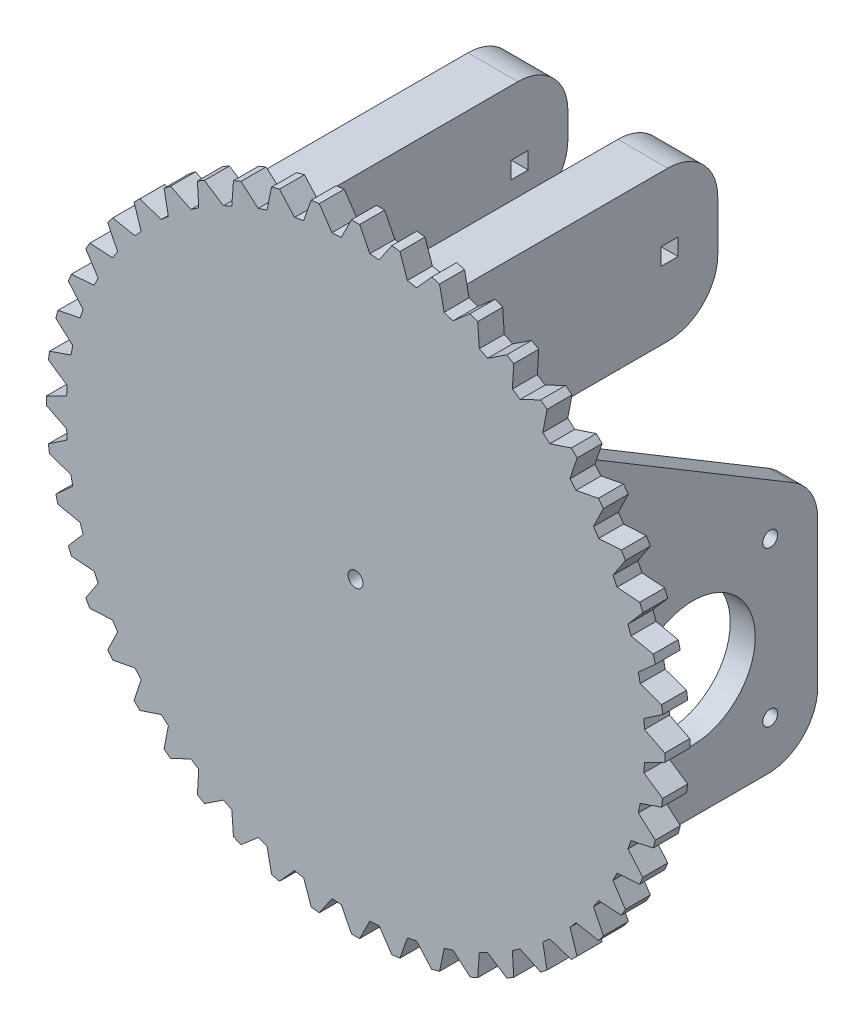
SolidWorks part; units mm, degrees
ref_plane "Front Plane" through (0, 0, 0) normal (0, 0, 1) x (1, 0, 0)
ref_plane "Top Plane" through (0, 0, 0) normal (0, 1, 0) x (1, 0, 0)
ref_plane "Right Plane" through (0, 0, 0) normal (1, 0, 0) x (0, 0, -1)
sketch "Sketch1" plane through (0, 0, 0) normal (0, 0, 1) x (1, 0, 0)
  circle A0 centre (0, 0) radius 60
  circle A1 centre (0, 0) radius 1.5
  dimension "D1" = 120
  dimension "D2" = 3
extrude "Boss-Extrude1" add sketch "Sketch1" along normal blind 5
sketch "Sketch2" plane through (0, 0, 0) normal (0, 0, -1) x (-1, 0, 0)
  line L0 (37.5, 37.5) -> (-37.5, -37.5) construction
  line L1 (-37.5, 37.5) -> (37.5, -37.5) construction
  line L3 (-37.5, 37.5) -> (-32.5, 37.5)
  line L4 (-37.5, 37.5) -> (-37.5, -37.5)
  line L5 (-37.5, -37.5) -> (-32.5, -37.5)
  line L6 (-32.5, 37.5) -> (-32.5, -37.5)
  line L7 (37.5, 37.5) -> (32.5, 37.5)
  line L8 (37.5, 37.5) -> (37.5, -37.5)
  line L9 (37.5, -37.5) -> (32.5, -37.5)
  line L10 (32.5, 37.5) -> (32.5, -37.5)
  point P7 (0, 0)
  dimension "D1" = 75
  dimension "D2" = 5
extrude "Boss-Extrude2" add sketch "Sketch2" along normal blind 50
sketch "Sketch3" plane through (32.5, 0, 0) normal (-1, 0, 0) x (0, 0, 1)
  line L0 (-50, -37.5) -> (0, 12.5) construction
  line L1 (-50, -37.5) -> (-50, 37.5) construction
  line L2 (-50, -37.5) -> (0, -37.5) construction
  line L3 (0, -37.5) -> (0, 37.5) construction
  line L4 (0, -37.5) -> (-50, 12.5) construction
  circle A0 centre (-40.5, 3) radius 1.5
  circle A1 centre (-9.5, 3) radius 1.5
  circle A2 centre (-9.5, -28) radius 1.5
  circle A3 centre (-40.5, -28) radius 1.5
  circle A4 centre (-25, -12.5) radius 12.5
  dimension "D2" = 3
  dimension "D4" = 25
  dimension "D1" = 45
  dimension "D3" = 31
extrude "Cut-Extrude1" cut sketch "Sketch3" against normal through all
sketch "Sketch6" plane through (-37.5, 0, 0) normal (-1, 0, 0) x (0, 0, 1)
  line L0 (-50, -37.5) -> (0, 12.5) construction
  line L1 (0, -37.5) -> (-50, 12.5) construction
  circle A0 centre (-40.5, 3) radius 1.5
  circle A1 centre (-9.5, 3) radius 1.5
  circle A2 centre (-9.5, -28) radius 1.5
  circle A3 centre (-40.5, -28) radius 1.5
  circle A4 centre (-25, -12.5) radius 12.5
  dimension "D1" = 3
  dimension "D3" = 25
  dimension "D2" = 31
extrude "Cut-Extrude5" cut sketch "Sketch6" against normal up to surface (5 mm away) up to face at (-32.5, 0, -25)
sketch "Sketch7" plane through (-37.5, 0, 0) normal (-1, 0, 0) x (0, 0, 1)
  line L0 (-25, -12.5) -> (-60.3553, 22.8553) construction
  line L1 (0, 60) -> (0, -60) construction
  line L2 (-50, 37.5) -> (-70, 37.5)
  line L3 (-70, 12.5) -> (-50, 12.5)
  line L4 (-50, -37.5) -> (-50, 37.5) construction
  line L5 (-70, 37.5) -> (-70, 12.5)
  line L6 (-50, 12.5) -> (-50, 37.5)
  line L7 (-58.6553, 21.1553) -> (-62.0553, 21.1553)
  line L8 (-58.6553, 21.1553) -> (-58.6553, 24.5553)
  line L9 (-58.6553, 24.5553) -> (-62.0553, 24.5553)
  line L10 (-62.0553, 21.1553) -> (-62.0553, 24.5553)
  line L11 (-58.6553, 21.1553) -> (-62.0553, 24.5553) construction
  line L12 (-58.6553, 24.5553) -> (-62.0553, 21.1553) construction
  circle A2 centre (-25, -12.5) radius 12.5 construction
  point P16 (-60.3553, 22.8553)
  dimension "D3" = 3.4
  dimension "D5" = 20
  dimension "D1" = 50
  dimension "D2" = 45
  dimension "D4" = 25
extrude "Boss-Extrude4" add sketch "Sketch7" against normal blind 5
sketch "Sketch8" plane through (-37.5, 0, 0) normal (-1, 0, 0) x (0, 0, 1)
  line L0 (-25, -12.5) -> (-25, 22.8553) construction
  line L1 (-25, 22.8553) -> (-60.3553, 22.8553) construction
  line L2 (-62.0553, 21.1553) -> (-58.6553, 24.5553) construction
sketch "Sketch10" plane through (0, 0, 0) normal (0, 0, -1) x (-1, 0, 0)
  line L1 (2.5, 37.5) -> (12.5, 37.5)
  line L2 (2.5, 37.5) -> (2.5, 7.5)
  line L3 (2.5, 7.5) -> (12.5, 7.5)
  line L4 (12.5, 37.5) -> (12.5, 7.5)
  line L5 (2.5, 37.5) -> (12.5, 7.5) construction
  line L6 (2.5, 7.5) -> (12.5, 37.5) construction
  line L9 (37.5, 37.5) -> (42.5, 37.5)
  line L10 (37.5, 37.5) -> (37.5, 12.5)
  line L11 (37.5, 12.5) -> (42.5, 12.5)
  line L12 (42.5, 37.5) -> (42.5, 12.5)
  point P0 (7.5, 22.5)
  dimension "D1" = 35
  dimension "D2" = 10
  dimension "D3" = 30
  dimension "D4" = 5
  dimension "D5" = 25
extrude "Boss-Extrude5" add sketch "Sketch10" along normal blind 70
sketch "Sketch13" plane through (-32.5, 0, 0) normal (-1, 0, 0) x (0, 0, 1)
  line L1 (-62.0553, 21.1553) -> (-58.6553, 21.1553)
  line L2 (-62.0553, 21.1553) -> (-62.0553, 24.5553)
  line L3 (-62.0553, 24.5553) -> (-58.6553, 24.5553)
  line L4 (-58.6553, 21.1553) -> (-58.6553, 24.5553)
extrude "Cut-Extrude7" cut sketch "Sketch13" against normal through all and the other way through all
fillet "Fillet1" radius 10 4 edges at (-7.5, 37.5, -70) (-7.5, 7.5, -70) (-37.5, 12.5, -70) (-37.5, 37.5, -70)
sketch "Sketch14" plane through (0, 0, -70) normal (0, 0, -1) x (-1, 0, 0)
  line L0 (12.5, 17.5) -> (2.5, 27.5) construction
  line L1 (7.5, 22.5) -> (37.5, 22.5) construction
  line L2 (32.5, 22.5) -> (42.5, 22.5) construction
  circle A0 centre (7.5, 22.5) radius 1.5
  circle A1 centre (37.5, 22.5) radius 1.5
  dimension "D1" = 3
extrude "Cut-Extrude8" cut sketch "Sketch14" against normal up to surface (11.3447 mm away) up to face at (-37.5, 22.8553, -58.6553)
chamfer "Chamfer1" distance 50 distance2 30 1 edges at (35, 37.5, -50) first distance on face at (35, 37.5, -25)
fillet "Fillet2" radius 10 4 edges at (35, 7.5, -50) (-35, -37.5, -50) (35, -37.5, -50) (-35, 12.5, -50)
sketch "Sketch16" plane through (0, 0, 5) normal (0, 0, 1) x (1, 0, 0)
  line L0 (0, 0) -> (0, 62) construction
  line L1 (0, 0) -> (-3.7934, 57.8758) construction
  line L2 (-3.7934, 57.8758) -> (-2.6384, 57.9515)
  line L3 (-2.6384, 57.9515) -> (-0.5787, 62)
  line L4 (-0.5787, 62) -> (0.5787, 62)
  line L5 (-17.2221, 59.5601) -> (14.0077, 60.3969) construction
  line L6 (-1.6608, 61.9778) -> (-1.5536, 57.9792) construction
  line L7 (2.6384, 57.9515) -> (0.5787, 62)
  line L8 (3.7934, 57.8758) -> (2.6384, 57.9515)
  line L9 (3.7934, 57.8758) -> (4.9483, 57.8001)
  line L10 (4.9483, 57.8001) -> (7.5189, 61.5451)
  line L11 (7.5189, 61.5451) -> (8.6664, 61.394)
  line L12 (10.18, 57.1114) -> (8.6664, 61.394)
  line L13 (11.3152, 56.8855) -> (10.18, 57.1114)
  line L14 (11.3152, 56.8855) -> (12.4504, 56.6597)
  line L15 (12.4504, 56.6597) -> (15.4878, 60.0372)
  line L16 (15.4878, 60.0372) -> (16.6058, 59.7376)
  line L17 (17.5475, 55.294) -> (16.6058, 59.7376)
  line L18 (18.6435, 54.9219) -> (17.5475, 55.294)
  line L19 (18.6435, 54.9219) -> (19.7395, 54.5499)
  line L20 (19.7395, 54.5499) -> (23.1917, 57.502)
  line L21 (23.1917, 57.502) -> (24.261, 57.0591)
  line L22 (24.6147, 52.5305) -> (24.261, 57.0591)
  line L23 (25.6527, 52.0186) -> (24.6147, 52.5305)
  line L24 (25.6527, 52.0186) -> (26.6908, 51.5067)
  line L25 (26.6908, 51.5067) -> (30.4988, 53.9829)
  line L26 (30.4988, 53.9829) -> (31.5012, 53.4042)
  line L27 (31.2607, 48.8683) -> (31.5012, 53.4042)
  line L28 (32.2231, 48.2252) -> (31.2607, 48.8683)
  line L29 (32.2231, 48.2252) -> (33.1855, 47.5822)
  line L30 (33.1855, 47.5822) -> (37.2841, 49.5402)
  line L31 (37.2841, 49.5402) -> (38.2023, 48.8356)
  line L32 (37.3718, 44.3699) -> (38.2023, 48.8356)
  line L33 (38.2421, 43.6067) -> (37.3718, 44.3699)
  line L34 (38.2421, 43.6067) -> (39.1123, 42.8436)
  line L35 (39.1123, 42.8436) -> (43.4314, 44.2498)
  line L36 (43.4314, 44.2498) -> (44.2498, 43.4314)
  line L37 (42.8436, 39.1123) -> (44.2498, 43.4314)
  line L38 (43.6067, 38.2421) -> (42.8436, 39.1123)
  line L39 (43.6067, 38.2421) -> (44.3699, 37.3718)
  line L40 (44.3699, 37.3718) -> (48.8356, 38.2023)
  line L41 (48.8356, 38.2023) -> (49.5402, 37.2841)
  line L42 (47.5822, 33.1855) -> (49.5402, 37.2841)
  line L43 (48.2252, 32.2231) -> (47.5822, 33.1855)
  line L44 (48.2252, 32.2231) -> (48.8683, 31.2607)
  line L45 (48.8683, 31.2607) -> (53.4042, 31.5012)
  line L46 (53.4042, 31.5012) -> (53.9829, 30.4988)
  line L47 (51.5067, 26.6908) -> (53.9829, 30.4988)
  line L48 (52.0186, 25.6527) -> (51.5067, 26.6908)
  line L49 (52.0186, 25.6527) -> (52.5305, 24.6147)
  line L50 (52.5305, 24.6147) -> (57.0591, 24.261)
  line L51 (57.0591, 24.261) -> (57.502, 23.1917)
  line L52 (54.5499, 19.7395) -> (57.502, 23.1917)
  line L53 (54.9219, 18.6435) -> (54.5499, 19.7395)
  line L54 (54.9219, 18.6435) -> (55.294, 17.5475)
  line L55 (55.294, 17.5475) -> (59.7376, 16.6058)
  line L56 (59.7376, 16.6058) -> (60.0372, 15.4878)
  line L57 (56.6597, 12.4504) -> (60.0372, 15.4878)
  line L58 (56.8855, 11.3152) -> (56.6597, 12.4504)
  line L59 (56.8855, 11.3152) -> (57.1114, 10.18)
  line L60 (57.1114, 10.18) -> (61.394, 8.6664)
  line L61 (61.394, 8.6664) -> (61.5451, 7.5189)
  line L62 (57.8001, 4.9483) -> (61.5451, 7.5189)
  line L63 (57.8758, 3.7934) -> (57.8001, 4.9483)
  line L64 (57.8758, 3.7934) -> (57.9515, 2.6384)
  line L65 (57.9515, 2.6384) -> (62, 0.5787)
  line L66 (62, 0.5787) -> (62, -0.5787)
  line L67 (57.9515, -2.6384) -> (62, -0.5787)
  line L68 (57.8758, -3.7934) -> (57.9515, -2.6384)
  line L69 (57.8758, -3.7934) -> (57.8001, -4.9483)
  line L70 (57.8001, -4.9483) -> (61.5451, -7.5189)
  line L71 (61.5451, -7.5189) -> (61.394, -8.6664)
  line L72 (57.1114, -10.18) -> (61.394, -8.6664)
  line L73 (56.8855, -11.3152) -> (57.1114, -10.18)
  line L74 (56.8855, -11.3152) -> (56.6597, -12.4504)
  line L75 (56.6597, -12.4504) -> (60.0372, -15.4878)
  line L76 (60.0372, -15.4878) -> (59.7376, -16.6058)
  line L77 (55.294, -17.5475) -> (59.7376, -16.6058)
  line L78 (54.9219, -18.6435) -> (55.294, -17.5475)
  line L79 (54.9219, -18.6435) -> (54.5499, -19.7395)
  line L80 (54.5499, -19.7395) -> (57.502, -23.1917)
  line L81 (57.502, -23.1917) -> (57.0591, -24.261)
  line L82 (52.5305, -24.6147) -> (57.0591, -24.261)
  line L83 (52.0186, -25.6527) -> (52.5305, -24.6147)
  line L84 (52.0186, -25.6527) -> (51.5067, -26.6908)
  line L85 (51.5067, -26.6908) -> (53.9829, -30.4988)
  line L86 (53.9829, -30.4988) -> (53.4042, -31.5012)
  line L87 (48.8683, -31.2607) -> (53.4042, -31.5012)
  line L88 (48.2252, -32.2231) -> (48.8683, -31.2607)
  line L89 (48.2252, -32.2231) -> (47.5822, -33.1855)
  line L90 (47.5822, -33.1855) -> (49.5402, -37.2841)
  line L91 (49.5402, -37.2841) -> (48.8356, -38.2023)
  line L92 (44.3699, -37.3718) -> (48.8356, -38.2023)
  line L93 (43.6067, -38.2421) -> (44.3699, -37.3718)
  line L94 (43.6067, -38.2421) -> (42.8436, -39.1123)
  line L95 (42.8436, -39.1123) -> (44.2498, -43.4314)
  line L96 (44.2498, -43.4314) -> (43.4314, -44.2498)
  line L97 (39.1123, -42.8436) -> (43.4314, -44.2498)
  line L98 (38.2421, -43.6067) -> (39.1123, -42.8436)
  line L99 (38.2421, -43.6067) -> (37.3718, -44.3699)
  line L100 (37.3718, -44.3699) -> (38.2023, -48.8356)
  line L101 (38.2023, -48.8356) -> (37.2841, -49.5402)
  line L102 (33.1855, -47.5822) -> (37.2841, -49.5402)
  line L103 (32.2231, -48.2252) -> (33.1855, -47.5822)
  line L104 (32.2231, -48.2252) -> (31.2607, -48.8683)
  line L105 (31.2607, -48.8683) -> (31.5012, -53.4042)
  line L106 (31.5012, -53.4042) -> (30.4988, -53.9829)
  line L107 (26.6908, -51.5067) -> (30.4988, -53.9829)
  line L108 (25.6527, -52.0186) -> (26.6908, -51.5067)
  line L109 (25.6527, -52.0186) -> (24.6147, -52.5305)
  line L110 (24.6147, -52.5305) -> (24.261, -57.0591)
  line L111 (24.261, -57.0591) -> (23.1917, -57.502)
  line L112 (19.7395, -54.5499) -> (23.1917, -57.502)
  line L113 (18.6435, -54.9219) -> (19.7395, -54.5499)
  line L114 (18.6435, -54.9219) -> (17.5475, -55.294)
  line L115 (17.5475, -55.294) -> (16.6058, -59.7376)
  line L116 (16.6058, -59.7376) -> (15.4878, -60.0372)
  line L117 (12.4504, -56.6597) -> (15.4878, -60.0372)
  line L118 (11.3152, -56.8855) -> (12.4504, -56.6597)
  line L119 (11.3152, -56.8855) -> (10.18, -57.1114)
  line L120 (10.18, -57.1114) -> (8.6664, -61.394)
  line L121 (8.6664, -61.394) -> (7.5189, -61.5451)
  line L122 (4.9483, -57.8001) -> (7.5189, -61.5451)
  line L123 (3.7934, -57.8758) -> (4.9483, -57.8001)
  line L124 (3.7934, -57.8758) -> (2.6384, -57.9515)
  line L125 (2.6384, -57.9515) -> (0.5787, -62)
  line L126 (0.5787, -62) -> (-0.5787, -62)
  line L127 (-2.6384, -57.9515) -> (-0.5787, -62)
  line L128 (-3.7934, -57.8758) -> (-2.6384, -57.9515)
  line L129 (-3.7934, -57.8758) -> (-4.9483, -57.8001)
  line L130 (-4.9483, -57.8001) -> (-7.5189, -61.5451)
  line L131 (-7.5189, -61.5451) -> (-8.6664, -61.394)
  line L132 (-10.18, -57.1114) -> (-8.6664, -61.394)
  line L133 (-11.3152, -56.8855) -> (-10.18, -57.1114)
  line L134 (-11.3152, -56.8855) -> (-12.4504, -56.6597)
  line L135 (-12.4504, -56.6597) -> (-15.4878, -60.0372)
  line L136 (-15.4878, -60.0372) -> (-16.6058, -59.7376)
  line L137 (-17.5475, -55.294) -> (-16.6058, -59.7376)
  line L138 (-18.6435, -54.9219) -> (-17.5475, -55.294)
  line L139 (-18.6435, -54.9219) -> (-19.7395, -54.5499)
  line L140 (-19.7395, -54.5499) -> (-23.1917, -57.502)
  line L141 (-23.1917, -57.502) -> (-24.261, -57.0591)
  line L142 (-24.6147, -52.5305) -> (-24.261, -57.0591)
  line L143 (-25.6527, -52.0186) -> (-24.6147, -52.5305)
  line L144 (-25.6527, -52.0186) -> (-26.6908, -51.5067)
  line L145 (-26.6908, -51.5067) -> (-30.4988, -53.9829)
  line L146 (-30.4988, -53.9829) -> (-31.5012, -53.4042)
  line L147 (-31.2607, -48.8683) -> (-31.5012, -53.4042)
  line L148 (-32.2231, -48.2252) -> (-31.2607, -48.8683)
  line L149 (-32.2231, -48.2252) -> (-33.1855, -47.5822)
  line L150 (-33.1855, -47.5822) -> (-37.2841, -49.5402)
  line L151 (-37.2841, -49.5402) -> (-38.2023, -48.8356)
  line L152 (-37.3718, -44.3699) -> (-38.2023, -48.8356)
  line L153 (-38.2421, -43.6067) -> (-37.3718, -44.3699)
  line L154 (-38.2421, -43.6067) -> (-39.1123, -42.8436)
  line L155 (-39.1123, -42.8436) -> (-43.4314, -44.2498)
  line L156 (-43.4314, -44.2498) -> (-44.2498, -43.4314)
  line L157 (-42.8436, -39.1123) -> (-44.2498, -43.4314)
  line L158 (-43.6067, -38.2421) -> (-42.8436, -39.1123)
  line L159 (-43.6067, -38.2421) -> (-44.3699, -37.3718)
  line L160 (-44.3699, -37.3718) -> (-48.8356, -38.2023)
  line L161 (-48.8356, -38.2023) -> (-49.5402, -37.2841)
  line L162 (-47.5822, -33.1855) -> (-49.5402, -37.2841)
  line L163 (-48.2252, -32.2231) -> (-47.5822, -33.1855)
  line L164 (-48.2252, -32.2231) -> (-48.8683, -31.2607)
  line L165 (-48.8683, -31.2607) -> (-53.4042, -31.5012)
  line L166 (-53.4042, -31.5012) -> (-53.9829, -30.4988)
  line L167 (-51.5067, -26.6908) -> (-53.9829, -30.4988)
  line L168 (-52.0186, -25.6527) -> (-51.5067, -26.6908)
  line L169 (-52.0186, -25.6527) -> (-52.5305, -24.6147)
  line L170 (-52.5305, -24.6147) -> (-57.0591, -24.261)
  line L171 (-57.0591, -24.261) -> (-57.502, -23.1917)
  line L172 (-54.5499, -19.7395) -> (-57.502, -23.1917)
  line L173 (-54.9219, -18.6435) -> (-54.5499, -19.7395)
  line L174 (-54.9219, -18.6435) -> (-55.294, -17.5475)
  line L175 (-55.294, -17.5475) -> (-59.7376, -16.6058)
  line L176 (-59.7376, -16.6058) -> (-60.0372, -15.4878)
  line L177 (-56.6597, -12.4504) -> (-60.0372, -15.4878)
  line L178 (-56.8855, -11.3152) -> (-56.6597, -12.4504)
  line L179 (-56.8855, -11.3152) -> (-57.1114, -10.18)
  line L180 (-57.1114, -10.18) -> (-61.394, -8.6664)
  line L181 (-61.394, -8.6664) -> (-61.5451, -7.5189)
  line L182 (-57.8001, -4.9483) -> (-61.5451, -7.5189)
  line L183 (-57.8758, -3.7934) -> (-57.8001, -4.9483)
  line L184 (-57.8758, -3.7934) -> (-57.9515, -2.6384)
  line L185 (-57.9515, -2.6384) -> (-62, -0.5787)
  line L186 (-62, -0.5787) -> (-62, 0.5787)
  line L187 (-57.9515, 2.6384) -> (-62, 0.5787)
  line L188 (-57.8758, 3.7934) -> (-57.9515, 2.6384)
  line L189 (-57.8758, 3.7934) -> (-57.8001, 4.9483)
  line L190 (-57.8001, 4.9483) -> (-61.5451, 7.5189)
  line L191 (-61.5451, 7.5189) -> (-61.394, 8.6664)
  line L192 (-57.1114, 10.18) -> (-61.394, 8.6664)
  line L193 (-56.8855, 11.3152) -> (-57.1114, 10.18)
  line L194 (-56.8855, 11.3152) -> (-56.6597, 12.4504)
  line L195 (-56.6597, 12.4504) -> (-60.0372, 15.4878)
  line L196 (-60.0372, 15.4878) -> (-59.7376, 16.6058)
  line L197 (-55.294, 17.5475) -> (-59.7376, 16.6058)
  line L198 (-54.9219, 18.6435) -> (-55.294, 17.5475)
  line L199 (-54.9219, 18.6435) -> (-54.5499, 19.7395)
  line L200 (-54.5499, 19.7395) -> (-57.502, 23.1917)
  line L201 (-57.502, 23.1917) -> (-57.0591, 24.261)
  line L202 (-52.5305, 24.6147) -> (-57.0591, 24.261)
  line L203 (-52.0186, 25.6527) -> (-52.5305, 24.6147)
  line L204 (-52.0186, 25.6527) -> (-51.5067, 26.6908)
  line L205 (-51.5067, 26.6908) -> (-53.9829, 30.4988)
  line L206 (-53.9829, 30.4988) -> (-53.4042, 31.5012)
  line L207 (-48.8683, 31.2607) -> (-53.4042, 31.5012)
  line L208 (-48.2252, 32.2231) -> (-48.8683, 31.2607)
  line L209 (-48.2252, 32.2231) -> (-47.5822, 33.1855)
  line L210 (-47.5822, 33.1855) -> (-49.5402, 37.2841)
  line L211 (-49.5402, 37.2841) -> (-48.8356, 38.2023)
  line L212 (-44.3699, 37.3718) -> (-48.8356, 38.2023)
  line L213 (-43.6067, 38.2421) -> (-44.3699, 37.3718)
  line L214 (-43.6067, 38.2421) -> (-42.8436, 39.1123)
  line L215 (-42.8436, 39.1123) -> (-44.2498, 43.4314)
  line L216 (-44.2498, 43.4314) -> (-43.4314, 44.2498)
  line L217 (-39.1123, 42.8436) -> (-43.4314, 44.2498)
  line L218 (-38.2421, 43.6067) -> (-39.1123, 42.8436)
  line L219 (-38.2421, 43.6067) -> (-37.3718, 44.3699)
  line L220 (-37.3718, 44.3699) -> (-38.2023, 48.8356)
  line L221 (-38.2023, 48.8356) -> (-37.2841, 49.5402)
  line L222 (-33.1855, 47.5822) -> (-37.2841, 49.5402)
  line L223 (-32.2231, 48.2252) -> (-33.1855, 47.5822)
  line L224 (-32.2231, 48.2252) -> (-31.2607, 48.8683)
  line L225 (-31.2607, 48.8683) -> (-31.5012, 53.4042)
  line L226 (-31.5012, 53.4042) -> (-30.4988, 53.9829)
  line L227 (-26.6908, 51.5067) -> (-30.4988, 53.9829)
  line L228 (-25.6527, 52.0186) -> (-26.6908, 51.5067)
  line L229 (-25.6527, 52.0186) -> (-24.6147, 52.5305)
  line L230 (-24.6147, 52.5305) -> (-24.261, 57.0591)
  line L231 (-24.261, 57.0591) -> (-23.1917, 57.502)
  line L232 (-19.7395, 54.5499) -> (-23.1917, 57.502)
  line L233 (-18.6435, 54.9219) -> (-19.7395, 54.5499)
  line L234 (-18.6435, 54.9219) -> (-17.5475, 55.294)
  line L235 (-17.5475, 55.294) -> (-16.6058, 59.7376)
  line L236 (-16.6058, 59.7376) -> (-15.4878, 60.0372)
  line L237 (-12.4504, 56.6597) -> (-15.4878, 60.0372)
  line L238 (-11.3152, 56.8855) -> (-12.4504, 56.6597)
  line L239 (-11.3152, 56.8855) -> (-10.18, 57.1114)
  line L240 (-10.18, 57.1114) -> (-8.6664, 61.394)
  line L241 (-8.6664, 61.394) -> (-7.5189, 61.5451)
  line L242 (-4.9483, 57.8001) -> (-7.5189, 61.5451)
  line L243 (-3.7934, 57.8758) -> (-4.9483, 57.8001)
  circle A3 centre (0, 0) radius 58
  circle A5 centre (0, 0) radius 62
  circle A6 centre (0, 0) radius 60 construction
  point P8 (-1.6072, 59.9785)
  point P302 (0, 0)
  circle M5 centre (0, 0) radius 1.5
  dimension "D1" = 3.75
  dimension "D2" = 2
  dimension "D3" = 2
  dimension "D4" = 28.5
  dimension "D5" = 48
extrude "Boss-Extrude6" add sketch "Sketch16" against normal up to surface (5 mm away) contours M5 | A5 region at (0, 0, 5) up to face at (-7.5, 22.5, 0)
sketch "Sketch18" plane through (0, 0, 0) normal (0, 0, 1) x (1, 0, 0)
  line L0 (0, 0) -> (0, 62) construction
  line L1 (0, 0) -> (-3.7934, 57.8758) construction
  line L2 (-3.7934, 57.8758) -> (-2.9199, 57.9331)
  line L3 (-2.9199, 57.9331) -> (-0.8754, 62)
  line L4 (-0.8754, 62) -> (0.8754, 62)
  line L5 (-17.5086, 59.4765) -> (13.7168, 60.4636) construction
  line L6 (-1.9591, 61.969) -> (-1.8327, 57.971) construction
  line L7 (2.9199, 57.9331) -> (0.8754, 62)
  line L8 (3.7934, 57.8758) -> (2.9199, 57.9331)
  line L9 (3.7934, 57.8758) -> (4.6669, 57.8186)
  line L10 (4.6669, 57.8186) -> (7.2247, 61.5838)
  line L11 (7.2247, 61.5838) -> (8.9605, 61.3553)
  line L12 (10.4567, 57.0563) -> (8.9605, 61.3553)
  line L13 (11.3152, 56.8855) -> (10.4567, 57.0563)
  line L14 (11.3152, 56.8855) -> (12.1738, 56.7148)
  line L15 (12.1738, 56.7148) -> (15.2012, 60.114)
  line L16 (15.2012, 60.114) -> (16.8923, 59.6608)
  line L17 (17.8146, 55.2033) -> (16.8923, 59.6608)
  line L18 (18.6435, 54.9219) -> (17.8146, 55.2033)
  line L19 (18.6435, 54.9219) -> (19.4724, 54.6406)
  line L20 (19.4724, 54.6406) -> (22.9176, 57.6155)
  line L21 (22.9176, 57.6155) -> (24.5351, 56.9455)
  line L22 (24.8676, 52.4058) -> (24.5351, 56.9455)
  line L23 (25.6527, 52.0186) -> (24.8676, 52.4058)
  line L24 (25.6527, 52.0186) -> (26.4378, 51.6314)
  line L25 (26.4378, 51.6314) -> (30.2419, 54.1313)
  line L26 (30.2419, 54.1313) -> (31.7581, 53.2559)
  line L27 (31.4952, 48.7116) -> (31.7581, 53.2559)
  line L28 (32.2231, 48.2252) -> (31.4952, 48.7116)
  line L29 (32.2231, 48.2252) -> (32.9509, 47.7389)
  line L30 (32.9509, 47.7389) -> (37.0487, 49.7208)
  line L31 (37.0487, 49.7208) -> (38.4377, 48.655)
  line L32 (37.5839, 44.1839) -> (38.4377, 48.655)
  line L33 (38.2421, 43.6067) -> (37.5839, 44.1839)
  line L34 (38.2421, 43.6067) -> (38.9002, 43.0295)
  line L35 (38.9002, 43.0295) -> (43.2216, 44.4596)
  line L36 (43.2216, 44.4596) -> (44.4596, 43.2216)
  line L37 (43.0295, 38.9002) -> (44.4596, 43.2216)
  line L38 (43.6067, 38.2421) -> (43.0295, 38.9002)
  line L39 (43.6067, 38.2421) -> (44.1839, 37.5839)
  line L40 (44.1839, 37.5839) -> (48.655, 38.4377)
  line L41 (48.655, 38.4377) -> (49.7208, 37.0487)
  line L42 (47.7389, 32.9509) -> (49.7208, 37.0487)
  line L43 (48.2252, 32.2231) -> (47.7389, 32.9509)
  line L44 (48.2252, 32.2231) -> (48.7116, 31.4952)
  line L45 (48.7116, 31.4952) -> (53.2559, 31.7581)
  line L46 (53.2559, 31.7581) -> (54.1313, 30.2419)
  line L47 (51.6314, 26.4378) -> (54.1313, 30.2419)
  line L48 (52.0186, 25.6527) -> (51.6314, 26.4378)
  line L49 (52.0186, 25.6527) -> (52.4058, 24.8676)
  line L50 (52.4058, 24.8676) -> (56.9455, 24.5351)
  line L51 (56.9455, 24.5351) -> (57.6155, 22.9176)
  line L52 (54.6406, 19.4724) -> (57.6155, 22.9176)
  line L53 (54.9219, 18.6435) -> (54.6406, 19.4724)
  line L54 (54.9219, 18.6435) -> (55.2033, 17.8146)
  line L55 (55.2033, 17.8146) -> (59.6608, 16.8923)
  line L56 (59.6608, 16.8923) -> (60.114, 15.2012)
  line L57 (56.7148, 12.1738) -> (60.114, 15.2012)
  line L58 (56.8855, 11.3152) -> (56.7148, 12.1738)
  line L59 (56.8855, 11.3152) -> (57.0563, 10.4567)
  line L60 (57.0563, 10.4567) -> (61.3553, 8.9605)
  line L61 (61.3553, 8.9605) -> (61.5838, 7.2247)
  line L62 (57.8186, 4.6669) -> (61.5838, 7.2247)
  line L63 (57.8758, 3.7934) -> (57.8186, 4.6669)
  line L64 (57.8758, 3.7934) -> (57.9331, 2.9199)
  line L65 (57.9331, 2.9199) -> (62, 0.8754)
  line L66 (62, 0.8754) -> (62, -0.8754)
  line L67 (57.9331, -2.9199) -> (62, -0.8754)
  line L68 (57.8758, -3.7934) -> (57.9331, -2.9199)
  line L69 (57.8758, -3.7934) -> (57.8186, -4.6669)
  line L70 (57.8186, -4.6669) -> (61.5838, -7.2247)
  line L71 (61.5838, -7.2247) -> (61.3553, -8.9605)
  line L72 (57.0563, -10.4567) -> (61.3553, -8.9605)
  line L73 (56.8855, -11.3152) -> (57.0563, -10.4567)
  line L74 (56.8855, -11.3152) -> (56.7148, -12.1738)
  line L75 (56.7148, -12.1738) -> (60.114, -15.2012)
  line L76 (60.114, -15.2012) -> (59.6608, -16.8923)
  line L77 (55.2033, -17.8146) -> (59.6608, -16.8923)
  line L78 (54.9219, -18.6435) -> (55.2033, -17.8146)
  line L79 (54.9219, -18.6435) -> (54.6406, -19.4724)
  line L80 (54.6406, -19.4724) -> (57.6155, -22.9176)
  line L81 (57.6155, -22.9176) -> (56.9455, -24.5351)
  line L82 (52.4058, -24.8676) -> (56.9455, -24.5351)
  line L83 (52.0186, -25.6527) -> (52.4058, -24.8676)
  line L84 (52.0186, -25.6527) -> (51.6314, -26.4378)
  line L85 (51.6314, -26.4378) -> (54.1313, -30.2419)
  line L86 (54.1313, -30.2419) -> (53.2559, -31.7581)
  line L87 (48.7116, -31.4952) -> (53.2559, -31.7581)
  line L88 (48.2252, -32.2231) -> (48.7116, -31.4952)
  line L89 (48.2252, -32.2231) -> (47.7389, -32.9509)
  line L90 (47.7389, -32.9509) -> (49.7208, -37.0487)
  line L91 (49.7208, -37.0487) -> (48.655, -38.4377)
  line L92 (44.1839, -37.5839) -> (48.655, -38.4377)
  line L93 (43.6067, -38.2421) -> (44.1839, -37.5839)
  line L94 (43.6067, -38.2421) -> (43.0295, -38.9002)
  line L95 (43.0295, -38.9002) -> (44.4596, -43.2216)
  line L96 (44.4596, -43.2216) -> (43.2216, -44.4596)
  line L97 (38.9002, -43.0295) -> (43.2216, -44.4596)
  line L98 (38.2421, -43.6067) -> (38.9002, -43.0295)
  line L99 (38.2421, -43.6067) -> (37.5839, -44.1839)
  line L100 (37.5839, -44.1839) -> (38.4377, -48.655)
  line L101 (38.4377, -48.655) -> (37.0487, -49.7208)
  line L102 (32.9509, -47.7389) -> (37.0487, -49.7208)
  line L103 (32.2231, -48.2252) -> (32.9509, -47.7389)
  line L104 (32.2231, -48.2252) -> (31.4952, -48.7116)
  line L105 (31.4952, -48.7116) -> (31.7581, -53.2559)
  line L106 (31.7581, -53.2559) -> (30.2419, -54.1313)
  line L107 (26.4378, -51.6314) -> (30.2419, -54.1313)
  line L108 (25.6527, -52.0186) -> (26.4378, -51.6314)
  line L109 (25.6527, -52.0186) -> (24.8676, -52.4058)
  line L110 (24.8676, -52.4058) -> (24.5351, -56.9455)
  line L111 (24.5351, -56.9455) -> (22.9176, -57.6155)
  line L112 (19.4724, -54.6406) -> (22.9176, -57.6155)
  line L113 (18.6435, -54.9219) -> (19.4724, -54.6406)
  line L114 (18.6435, -54.9219) -> (17.8146, -55.2033)
  line L115 (17.8146, -55.2033) -> (16.8923, -59.6608)
  line L116 (16.8923, -59.6608) -> (15.2012, -60.114)
  line L117 (12.1738, -56.7148) -> (15.2012, -60.114)
  line L118 (11.3152, -56.8855) -> (12.1738, -56.7148)
  line L119 (11.3152, -56.8855) -> (10.4567, -57.0563)
  line L120 (10.4567, -57.0563) -> (8.9605, -61.3553)
  line L121 (8.9605, -61.3553) -> (7.2247, -61.5838)
  line L122 (4.6669, -57.8186) -> (7.2247, -61.5838)
  line L123 (3.7934, -57.8758) -> (4.6669, -57.8186)
  line L124 (3.7934, -57.8758) -> (2.9199, -57.9331)
  line L125 (2.9199, -57.9331) -> (0.8754, -62)
  line L126 (0.8754, -62) -> (-0.8754, -62)
  line L127 (-2.9199, -57.9331) -> (-0.8754, -62)
  line L128 (-3.7934, -57.8758) -> (-2.9199, -57.9331)
  line L129 (-3.7934, -57.8758) -> (-4.6669, -57.8186)
  line L130 (-4.6669, -57.8186) -> (-7.2247, -61.5838)
  line L131 (-7.2247, -61.5838) -> (-8.9605, -61.3553)
  line L132 (-10.4567, -57.0563) -> (-8.9605, -61.3553)
  line L133 (-11.3152, -56.8855) -> (-10.4567, -57.0563)
  line L134 (-11.3152, -56.8855) -> (-12.1738, -56.7148)
  line L135 (-12.1738, -56.7148) -> (-15.2012, -60.114)
  line L136 (-15.2012, -60.114) -> (-16.8923, -59.6608)
  line L137 (-17.8146, -55.2033) -> (-16.8923, -59.6608)
  line L138 (-18.6435, -54.9219) -> (-17.8146, -55.2033)
  line L139 (-18.6435, -54.9219) -> (-19.4724, -54.6406)
  line L140 (-19.4724, -54.6406) -> (-22.9176, -57.6155)
  line L141 (-22.9176, -57.6155) -> (-24.5351, -56.9455)
  line L142 (-24.8676, -52.4058) -> (-24.5351, -56.9455)
  line L143 (-25.6527, -52.0186) -> (-24.8676, -52.4058)
  line L144 (-25.6527, -52.0186) -> (-26.4378, -51.6314)
  line L145 (-26.4378, -51.6314) -> (-30.2419, -54.1313)
  line L146 (-30.2419, -54.1313) -> (-31.7581, -53.2559)
  line L147 (-31.4952, -48.7116) -> (-31.7581, -53.2559)
  line L148 (-32.2231, -48.2252) -> (-31.4952, -48.7116)
  line L149 (-32.2231, -48.2252) -> (-32.9509, -47.7389)
  line L150 (-32.9509, -47.7389) -> (-37.0487, -49.7208)
  line L151 (-37.0487, -49.7208) -> (-38.4377, -48.655)
  line L152 (-37.5839, -44.1839) -> (-38.4377, -48.655)
  line L153 (-38.2421, -43.6067) -> (-37.5839, -44.1839)
  line L154 (-38.2421, -43.6067) -> (-38.9002, -43.0295)
  line L155 (-38.9002, -43.0295) -> (-43.2216, -44.4596)
  line L156 (-43.2216, -44.4596) -> (-44.4596, -43.2216)
  line L157 (-43.0295, -38.9002) -> (-44.4596, -43.2216)
  line L158 (-43.6067, -38.2421) -> (-43.0295, -38.9002)
  line L159 (-43.6067, -38.2421) -> (-44.1839, -37.5839)
  line L160 (-44.1839, -37.5839) -> (-48.655, -38.4377)
  line L161 (-48.655, -38.4377) -> (-49.7208, -37.0487)
  line L162 (-47.7389, -32.9509) -> (-49.7208, -37.0487)
  line L163 (-48.2252, -32.2231) -> (-47.7389, -32.9509)
  line L164 (-48.2252, -32.2231) -> (-48.7116, -31.4952)
  line L165 (-48.7116, -31.4952) -> (-53.2559, -31.7581)
  line L166 (-53.2559, -31.7581) -> (-54.1313, -30.2419)
  line L167 (-51.6314, -26.4378) -> (-54.1313, -30.2419)
  line L168 (-52.0186, -25.6527) -> (-51.6314, -26.4378)
  line L169 (-52.0186, -25.6527) -> (-52.4058, -24.8676)
  line L170 (-52.4058, -24.8676) -> (-56.9455, -24.5351)
  line L171 (-56.9455, -24.5351) -> (-57.6155, -22.9176)
  line L172 (-54.6406, -19.4724) -> (-57.6155, -22.9176)
  line L173 (-54.9219, -18.6435) -> (-54.6406, -19.4724)
  line L174 (-54.9219, -18.6435) -> (-55.2033, -17.8146)
  line L175 (-55.2033, -17.8146) -> (-59.6608, -16.8923)
  line L176 (-59.6608, -16.8923) -> (-60.114, -15.2012)
  line L177 (-56.7148, -12.1738) -> (-60.114, -15.2012)
  line L178 (-56.8855, -11.3152) -> (-56.7148, -12.1738)
  line L179 (-56.8855, -11.3152) -> (-57.0563, -10.4567)
  line L180 (-57.0563, -10.4567) -> (-61.3553, -8.9605)
  line L181 (-61.3553, -8.9605) -> (-61.5838, -7.2247)
  line L182 (-57.8186, -4.6669) -> (-61.5838, -7.2247)
  line L183 (-57.8758, -3.7934) -> (-57.8186, -4.6669)
  line L184 (-57.8758, -3.7934) -> (-57.9331, -2.9199)
  line L185 (-57.9331, -2.9199) -> (-62, -0.8754)
  line L186 (-62, -0.8754) -> (-62, 0.8754)
  line L187 (-57.9331, 2.9199) -> (-62, 0.8754)
  line L188 (-57.8758, 3.7934) -> (-57.9331, 2.9199)
  line L189 (-57.8758, 3.7934) -> (-57.8186, 4.6669)
  line L190 (-57.8186, 4.6669) -> (-61.5838, 7.2247)
  line L191 (-61.5838, 7.2247) -> (-61.3553, 8.9605)
  line L192 (-57.0563, 10.4567) -> (-61.3553, 8.9605)
  line L193 (-56.8855, 11.3152) -> (-57.0563, 10.4567)
  line L194 (-56.8855, 11.3152) -> (-56.7148, 12.1738)
  line L195 (-56.7148, 12.1738) -> (-60.114, 15.2012)
  line L196 (-60.114, 15.2012) -> (-59.6608, 16.8923)
  line L197 (-55.2033, 17.8146) -> (-59.6608, 16.8923)
  line L198 (-54.9219, 18.6435) -> (-55.2033, 17.8146)
  line L199 (-54.9219, 18.6435) -> (-54.6406, 19.4724)
  line L200 (-54.6406, 19.4724) -> (-57.6155, 22.9176)
  line L201 (-57.6155, 22.9176) -> (-56.9455, 24.5351)
  line L202 (-52.4058, 24.8676) -> (-56.9455, 24.5351)
  line L203 (-52.0186, 25.6527) -> (-52.4058, 24.8676)
  line L204 (-52.0186, 25.6527) -> (-51.6314, 26.4378)
  line L205 (-51.6314, 26.4378) -> (-54.1313, 30.2419)
  line L206 (-54.1313, 30.2419) -> (-53.2559, 31.7581)
  line L207 (-48.7116, 31.4952) -> (-53.2559, 31.7581)
  line L208 (-48.2252, 32.2231) -> (-48.7116, 31.4952)
  line L209 (-48.2252, 32.2231) -> (-47.7389, 32.9509)
  line L210 (-47.7389, 32.9509) -> (-49.7208, 37.0487)
  line L211 (-49.7208, 37.0487) -> (-48.655, 38.4377)
  line L212 (-44.1839, 37.5839) -> (-48.655, 38.4377)
  line L213 (-43.6067, 38.2421) -> (-44.1839, 37.5839)
  line L214 (-43.6067, 38.2421) -> (-43.0295, 38.9002)
  line L215 (-43.0295, 38.9002) -> (-44.4596, 43.2216)
  line L216 (-44.4596, 43.2216) -> (-43.2216, 44.4596)
  line L217 (-38.9002, 43.0295) -> (-43.2216, 44.4596)
  line L218 (-38.2421, 43.6067) -> (-38.9002, 43.0295)
  line L219 (-38.2421, 43.6067) -> (-37.5839, 44.1839)
  line L220 (-37.5839, 44.1839) -> (-38.4377, 48.655)
  line L221 (-38.4377, 48.655) -> (-37.0487, 49.7208)
  line L222 (-32.9509, 47.7389) -> (-37.0487, 49.7208)
  line L223 (-32.2231, 48.2252) -> (-32.9509, 47.7389)
  line L224 (-32.2231, 48.2252) -> (-31.4952, 48.7116)
  line L225 (-31.4952, 48.7116) -> (-31.7581, 53.2559)
  line L226 (-31.7581, 53.2559) -> (-30.2419, 54.1313)
  line L227 (-26.4378, 51.6314) -> (-30.2419, 54.1313)
  line L228 (-25.6527, 52.0186) -> (-26.4378, 51.6314)
  line L229 (-25.6527, 52.0186) -> (-24.8676, 52.4058)
  line L230 (-24.8676, 52.4058) -> (-24.5351, 56.9455)
  line L231 (-24.5351, 56.9455) -> (-22.9176, 57.6155)
  line L232 (-19.4724, 54.6406) -> (-22.9176, 57.6155)
  line L233 (-18.6435, 54.9219) -> (-19.4724, 54.6406)
  line L234 (-18.6435, 54.9219) -> (-17.8146, 55.2033)
  line L235 (-17.8146, 55.2033) -> (-16.8923, 59.6608)
  line L236 (-16.8923, 59.6608) -> (-15.2012, 60.114)
  line L237 (-12.1738, 56.7148) -> (-15.2012, 60.114)
  line L238 (-11.3152, 56.8855) -> (-12.1738, 56.7148)
  line L239 (-11.3152, 56.8855) -> (-10.4567, 57.0563)
  line L240 (-10.4567, 57.0563) -> (-8.9605, 61.3553)
  line L241 (-8.9605, 61.3553) -> (-7.2247, 61.5838)
  line L242 (-4.6669, 57.8186) -> (-7.2247, 61.5838)
  line L243 (-3.7934, 57.8758) -> (-4.6669, 57.8186)
  line L244 (0, 62) -> (0, 62.9939) construction
  line L245 (0, 62.9939) -> (-0.8754, 62.9939) construction
  line L246 (-0.8754, 62.9939) -> (-0.8754, 62) construction
  circle A3 centre (0, 0) radius 58 construction
  circle A4 centre (0, 0) radius 63
  circle A5 centre (0, 0) radius 62 construction
  circle A6 centre (0, 0) radius 62 construction
  circle A7 centre (0, 0) radius 60 construction
  point P8 (-1.8959, 59.97)
  point P22 (-0.7794, 63.5585)
  point P26 (-0.8754, 62.9939)
  point P32 (0, 0)
  point P38 (0, 0)
  point P302 (0, 0)
  dimension "D1" = 3.75
  dimension "D2" = 1
  dimension "D3" = 120
  dimension "D6" = 2
  dimension "D7" = 120
  dimension "D8" = 2
  dimension "D9" = 2
  dimension "D4" = 28.5
  dimension "D5" = 48
extrude "Cut-Extrude10" cut sketch "Sketch18" along normal up to surface (5 mm away) contours A4 L243 L2 L3 L4 L7 L8 L9 L10 L11 L12 L13 L14 L15 L16 L17 L18 L19 L20 L21 L22 L23 L24 L25 L26 L27 L28 L29 L30 L31 L32 L33 L34 L35 L36 L37 L38 L39 L40 L41 L42 L43 L44 L45 L46 L47 L48 L49 L50 L51 region at (-62.8218, 0, 0) up to face at (1.5, 0, 5)
sketch "Sketch22" plane through (0, 0, 5) normal (0, 0, 1) x (1, 0, 0)
  line L0 (0, 0) -> (0, 62) construction
  line L1 (0, 0) -> (-0.8785, 61.9938) construction
  line L2 (4.7174, 57.715) -> (2.8562, 57.837)
  line L3 (7.2694, 61.4717) -> (4.7174, 57.715)
  line L4 (10.381, 56.9694) -> (8.8883, 61.2585)
  line L5 (12.2104, 56.6055) -> (10.381, 56.9694)
  line L6 (15.2309, 59.9969) -> (12.2104, 56.6055)
  line L7 (17.7282, 55.127) -> (16.8081, 59.5743)
  line L8 (19.4945, 54.5275) -> (17.7282, 55.127)
  line L9 (22.9318, 57.4956) -> (19.4945, 54.5275)
  line L10 (24.7721, 52.3414) -> (24.4403, 56.8707)
  line L11 (26.4449, 51.5165) -> (24.7721, 52.3414)
  line L12 (30.2403, 54.0105) -> (26.4449, 51.5165)
  line L13 (31.3921, 48.6602) -> (31.6544, 53.1941)
  line L14 (32.9429, 47.624) -> (31.3921, 48.6602)
  line L15 (37.0313, 49.6013) -> (32.9429, 47.624)
  line L16 (37.475, 44.1464) -> (38.3268, 48.6073)
  line L17 (38.8773, 42.9166) -> (37.475, 44.1464)
  line L18 (43.1888, 44.3434) -> (38.8773, 42.9166)
  line L19 (42.9166, 38.8773) -> (44.3434, 43.1888)
  line L20 (44.1464, 37.475) -> (42.9166, 38.8773)
  line L21 (48.6073, 38.3268) -> (44.1464, 37.475)
  line L22 (47.624, 32.9429) -> (49.6013, 37.0313)
  line L23 (48.6602, 31.3921) -> (47.624, 32.9429)
  line L24 (53.1941, 31.6544) -> (48.6602, 31.3921)
  line L25 (51.5165, 26.4449) -> (54.0105, 30.2403)
  line L26 (52.3414, 24.7721) -> (51.5165, 26.4449)
  line L27 (56.8707, 24.4403) -> (52.3414, 24.7721)
  line L28 (54.5275, 19.4945) -> (57.4956, 22.9318)
  line L29 (55.127, 17.7282) -> (54.5275, 19.4945)
  line L30 (59.5743, 16.8081) -> (55.127, 17.7282)
  line L31 (56.6055, 12.2104) -> (59.9969, 15.2309)
  line L32 (4.6603, 57.7188) -> (2.8562, 57.837)
  line L33 (2.8562, 57.837) -> (0.8164, 61.8946)
  line L34 (-0.8164, 61.8946) -> (-2.8562, 57.837)
  line L35 (-2.8562, 57.837) -> (-4.7174, 57.715)
  line L36 (-4.7174, 57.715) -> (-7.3035, 61.5219)
  line L37 (4.6603, 57.7188) -> (2.8562, 57.837) construction
  line L38 (2.8562, 57.837) -> (0.8164, 61.8946)
  line L39 (-0.8164, 61.8946) -> (-2.8562, 57.837)
  line L40 (-2.8562, 57.837) -> (-4.7174, 57.715)
  line L41 (-4.7174, 57.715) -> (-7.3035, 61.5219) construction
  line L42 (56.9694, 10.381) -> (56.6055, 12.2104)
  line L43 (61.2585, 8.8883) -> (56.9694, 10.381)
  line L44 (57.715, 4.7174) -> (61.4717, 7.2694)
  line L45 (57.837, 2.8562) -> (57.715, 4.7174)
  line L46 (61.8946, 0.8164) -> (57.837, 2.8562)
  line L47 (57.837, -2.8562) -> (61.8946, -0.8164)
  line L48 (57.715, -4.7174) -> (57.837, -2.8562)
  line L49 (61.4717, -7.2694) -> (57.715, -4.7174)
  line L50 (56.9694, -10.381) -> (61.2585, -8.8883)
  line L51 (56.6055, -12.2104) -> (56.9694, -10.381)
  line L52 (59.9969, -15.2309) -> (56.6055, -12.2104)
  line L53 (55.127, -17.7282) -> (59.5743, -16.8081)
  line L54 (54.5275, -19.4945) -> (55.127, -17.7282)
  line L55 (57.4956, -22.9318) -> (54.5275, -19.4945)
  line L56 (52.3414, -24.7721) -> (56.8707, -24.4403)
  line L57 (51.5165, -26.4449) -> (52.3414, -24.7721)
  line L58 (54.0105, -30.2403) -> (51.5165, -26.4449)
  line L59 (48.6602, -31.3921) -> (53.1941, -31.6544)
  line L60 (47.624, -32.9429) -> (48.6602, -31.3921)
  line L61 (49.6013, -37.0313) -> (47.624, -32.9429)
  line L62 (44.1464, -37.475) -> (48.6073, -38.3268)
  line L63 (42.9166, -38.8773) -> (44.1464, -37.475)
  line L64 (44.3434, -43.1888) -> (42.9166, -38.8773)
  line L65 (38.8773, -42.9166) -> (43.1888, -44.3434)
  line L66 (37.475, -44.1464) -> (38.8773, -42.9166)
  line L67 (38.3268, -48.6073) -> (37.475, -44.1464)
  line L68 (32.9429, -47.624) -> (37.0313, -49.6013)
  line L69 (31.3921, -48.6602) -> (32.9429, -47.624)
  line L70 (31.6544, -53.1941) -> (31.3921, -48.6602)
  line L71 (26.4449, -51.5165) -> (30.2403, -54.0105)
  line L72 (24.7721, -52.3414) -> (26.4449, -51.5165)
  line L73 (24.4403, -56.8707) -> (24.7721, -52.3414)
  line L74 (19.4945, -54.5275) -> (22.9318, -57.4956)
  line L75 (17.7282, -55.127) -> (19.4945, -54.5275)
  line L76 (16.8081, -59.5743) -> (17.7282, -55.127)
  line L77 (12.2104, -56.6055) -> (15.2309, -59.9969)
  line L78 (10.381, -56.9694) -> (12.2104, -56.6055)
  line L79 (8.8883, -61.2585) -> (10.381, -56.9694)
  line L80 (4.7174, -57.715) -> (7.2694, -61.4717)
  line L81 (2.8562, -57.837) -> (4.7174, -57.715)
  line L82 (0.8164, -61.8946) -> (2.8562, -57.837)
  line L83 (-2.8562, -57.837) -> (-0.8164, -61.8946)
  line L84 (-4.7174, -57.715) -> (-2.8562, -57.837)
  line L85 (-7.2694, -61.4717) -> (-4.7174, -57.715)
  line L86 (-10.381, -56.9694) -> (-8.8883, -61.2585)
  line L87 (-12.2104, -56.6055) -> (-10.381, -56.9694)
  line L88 (-15.2309, -59.9969) -> (-12.2104, -56.6055)
  line L89 (-17.7282, -55.127) -> (-16.8081, -59.5743)
  line L90 (-19.4945, -54.5275) -> (-17.7282, -55.127)
  line L91 (-22.9318, -57.4956) -> (-19.4945, -54.5275)
  line L92 (-24.7721, -52.3414) -> (-24.4403, -56.8707)
  line L93 (-26.4449, -51.5165) -> (-24.7721, -52.3414)
  line L94 (-30.2403, -54.0105) -> (-26.4449, -51.5165)
  line L95 (-31.3921, -48.6602) -> (-31.6544, -53.1941)
  line L96 (-32.9429, -47.624) -> (-31.3921, -48.6602)
  line L97 (-37.0313, -49.6013) -> (-32.9429, -47.624)
  line L98 (-37.475, -44.1464) -> (-38.3268, -48.6073)
  line L99 (-38.8773, -42.9166) -> (-37.475, -44.1464)
  line L100 (-43.1888, -44.3434) -> (-38.8773, -42.9166)
  line L101 (-42.9166, -38.8773) -> (-44.3434, -43.1888)
  line L102 (-44.1464, -37.475) -> (-42.9166, -38.8773)
  line L103 (-48.6073, -38.3268) -> (-44.1464, -37.475)
  line L104 (-47.624, -32.9429) -> (-49.6013, -37.0313)
  line L105 (-48.6602, -31.3921) -> (-47.624, -32.9429)
  line L106 (-53.1941, -31.6544) -> (-48.6602, -31.3921)
  line L107 (-51.5165, -26.4449) -> (-54.0105, -30.2403)
  line L108 (-52.3414, -24.7721) -> (-51.5165, -26.4449)
  line L109 (-56.8707, -24.4403) -> (-52.3414, -24.7721)
  line L110 (-54.5275, -19.4945) -> (-57.4956, -22.9318)
  line L111 (-55.127, -17.7282) -> (-54.5275, -19.4945)
  line L112 (-59.5743, -16.8081) -> (-55.127, -17.7282)
  line L113 (-56.6055, -12.2104) -> (-59.9969, -15.2309)
  line L114 (-56.9694, -10.381) -> (-56.6055, -12.2104)
  line L115 (-61.2585, -8.8883) -> (-56.9694, -10.381)
  line L116 (-57.715, -4.7174) -> (-61.4717, -7.2694)
  line L117 (-57.837, -2.8562) -> (-57.715, -4.7174)
  line L118 (-61.8946, -0.8164) -> (-57.837, -2.8562)
  line L119 (-57.837, 2.8562) -> (-61.8946, 0.8164)
  line L120 (-57.715, 4.7174) -> (-57.837, 2.8562)
  line L121 (-61.4717, 7.2694) -> (-57.715, 4.7174)
  line L122 (-56.9694, 10.381) -> (-61.2585, 8.8883)
  line L123 (-56.6055, 12.2104) -> (-56.9694, 10.381)
  line L124 (-59.9969, 15.2309) -> (-56.6055, 12.2104)
  line L125 (-55.127, 17.7282) -> (-59.5743, 16.8081)
  line L126 (-54.5275, 19.4945) -> (-55.127, 17.7282)
  line L127 (-57.4956, 22.9318) -> (-54.5275, 19.4945)
  line L128 (-52.3414, 24.7721) -> (-56.8707, 24.4403)
  line L129 (-51.5165, 26.4449) -> (-52.3414, 24.7721)
  line L130 (-54.0105, 30.2403) -> (-51.5165, 26.4449)
  line L131 (-48.6602, 31.3921) -> (-53.1941, 31.6544)
  line L132 (-47.624, 32.9429) -> (-48.6602, 31.3921)
  line L133 (-49.6013, 37.0313) -> (-47.624, 32.9429)
  line L134 (-44.1464, 37.475) -> (-48.6073, 38.3268)
  line L135 (-42.9166, 38.8773) -> (-44.1464, 37.475)
  line L136 (-44.3434, 43.1888) -> (-42.9166, 38.8773)
  line L137 (-38.8773, 42.9166) -> (-43.1888, 44.3434)
  line L138 (-37.475, 44.1464) -> (-38.8773, 42.9166)
  line L139 (-38.3268, 48.6073) -> (-37.475, 44.1464)
  line L140 (-32.9429, 47.624) -> (-37.0313, 49.6013)
  line L141 (-31.3921, 48.6602) -> (-32.9429, 47.624)
  line L142 (-31.6544, 53.1941) -> (-31.3921, 48.6602)
  line L143 (-26.4449, 51.5165) -> (-30.2403, 54.0105)
  line L144 (-24.7721, 52.3414) -> (-26.4449, 51.5165)
  line L145 (-24.4403, 56.8707) -> (-24.7721, 52.3414)
  line L146 (-19.4945, 54.5275) -> (-22.9318, 57.4956)
  line L147 (-17.7282, 55.127) -> (-19.4945, 54.5275)
  line L148 (-16.8081, 59.5743) -> (-17.7282, 55.127)
  line L149 (-12.2104, 56.6055) -> (-15.2309, 59.9969)
  line L150 (-10.381, 56.9694) -> (-12.2104, 56.6055)
  line L151 (-8.8883, 61.2585) -> (-10.381, 56.9694)
  line L152 (-4.7174, 57.715) -> (-7.2694, 61.4717)
  arc A0 (0.8785, 61.9938) -> (-0.8785, 61.9938) centre (0, 0) ccw construction
  arc A1 (8.8883, 61.2585) -> (7.2694, 61.4717) centre (0, 0) ccw
  arc A2 (16.8081, 59.5743) -> (15.2309, 59.9969) centre (0, 0) ccw
  arc A3 (24.4403, 56.8707) -> (22.9318, 57.4956) centre (0, 0) ccw
  arc A4 (31.6544, 53.1941) -> (30.2403, 54.0105) centre (0, 0) ccw
  arc A5 (38.3268, 48.6073) -> (37.0313, 49.6013) centre (0, 0) ccw
  arc A6 (44.3434, 43.1888) -> (43.1888, 44.3434) centre (0, 0) ccw
  arc A7 (49.6013, 37.0313) -> (48.6073, 38.3268) centre (0, 0) ccw
  arc A8 (0.8164, 61.8946) -> (-0.8164, 61.8946) centre (0, 0) ccw
  arc A9 (0.8164, 61.8946) -> (-0.8164, 61.8946) centre (0, 0) ccw
  arc A10 (54.0105, 30.2403) -> (53.1941, 31.6544) centre (0, 0) ccw
  arc A11 (57.4956, 22.9318) -> (56.8707, 24.4403) centre (0, 0) ccw
  arc A12 (59.9969, 15.2309) -> (59.5743, 16.8081) centre (0, 0) ccw
  arc A13 (61.4717, 7.2694) -> (61.2585, 8.8883) centre (0, 0) ccw
  arc A14 (61.8946, -0.8164) -> (61.8946, 0.8164) centre (0, 0) ccw
  arc A15 (61.2585, -8.8883) -> (61.4717, -7.2694) centre (0, 0) ccw
  arc A16 (59.5743, -16.8081) -> (59.9969, -15.2309) centre (0, 0) ccw
  arc A17 (56.8707, -24.4403) -> (57.4956, -22.9318) centre (0, 0) ccw
  arc A18 (53.1941, -31.6544) -> (54.0105, -30.2403) centre (0, 0) ccw
  arc A19 (48.6073, -38.3268) -> (49.6013, -37.0313) centre (0, 0) ccw
  arc A20 (43.1888, -44.3434) -> (44.3434, -43.1888) centre (0, 0) ccw
  arc A21 (37.0313, -49.6013) -> (38.3268, -48.6073) centre (0, 0) ccw
  arc A22 (30.2403, -54.0105) -> (31.6544, -53.1941) centre (0, 0) ccw
  arc A23 (22.9318, -57.4956) -> (24.4403, -56.8707) centre (0, 0) ccw
  arc A24 (15.2309, -59.9969) -> (16.8081, -59.5743) centre (0, 0) ccw
  arc A25 (7.2694, -61.4717) -> (8.8883, -61.2585) centre (0, 0) ccw
  arc A26 (-0.8164, -61.8946) -> (0.8164, -61.8946) centre (0, 0) ccw
  arc A27 (-8.8883, -61.2585) -> (-7.2694, -61.4717) centre (0, 0) ccw
  arc A28 (-16.8081, -59.5743) -> (-15.2309, -59.9969) centre (0, 0) ccw
  arc A29 (-24.4403, -56.8707) -> (-22.9318, -57.4956) centre (0, 0) ccw
  arc A30 (-31.6544, -53.1941) -> (-30.2403, -54.0105) centre (0, 0) ccw
  arc A31 (-38.3268, -48.6073) -> (-37.0313, -49.6013) centre (0, 0) ccw
  arc A32 (-44.3434, -43.1888) -> (-43.1888, -44.3434) centre (0, 0) ccw
  arc A33 (-49.6013, -37.0313) -> (-48.6073, -38.3268) centre (0, 0) ccw
  arc A34 (-54.0105, -30.2403) -> (-53.1941, -31.6544) centre (0, 0) ccw
  arc A35 (-57.4956, -22.9318) -> (-56.8707, -24.4403) centre (0, 0) ccw
  arc A36 (-59.9969, -15.2309) -> (-59.5743, -16.8081) centre (0, 0) ccw
  arc A37 (-61.4717, -7.2694) -> (-61.2585, -8.8883) centre (0, 0) ccw
  arc A38 (-61.8946, 0.8164) -> (-61.8946, -0.8164) centre (0, 0) ccw
  arc A39 (-61.2585, 8.8883) -> (-61.4717, 7.2694) centre (0, 0) ccw
  arc A40 (-59.5743, 16.8081) -> (-59.9969, 15.2309) centre (0, 0) ccw
  arc A41 (-56.8707, 24.4403) -> (-57.4956, 22.9318) centre (0, 0) ccw
  arc A42 (-53.1941, 31.6544) -> (-54.0105, 30.2403) centre (0, 0) ccw
  arc A43 (-48.6073, 38.3268) -> (-49.6013, 37.0313) centre (0, 0) ccw
  arc A44 (-43.1888, 44.3434) -> (-44.3434, 43.1888) centre (0, 0) ccw
  arc A45 (-37.0313, 49.6013) -> (-38.3268, 48.6073) centre (0, 0) ccw
  arc A46 (-30.2403, 54.0105) -> (-31.6544, 53.1941) centre (0, 0) ccw
  arc A47 (-22.9318, 57.4956) -> (-24.4403, 56.8707) centre (0, 0) ccw
  arc A48 (-15.2309, 59.9969) -> (-16.8081, 59.5743) centre (0, 0) ccw
  arc A49 (-7.2694, 61.4717) -> (-8.8883, 61.2585) centre (0, 0) ccw
  circle A50 centre (0, 0) radius 65
  point P253 (0, 0)
  dimension "D2" = 130
  dimension "D1" = 0.1
extrude "Cut-Extrude13" cut sketch "Sketch22" against normal up to surface (5 mm away) contours A50 A49 L152 L40 L39 A9 L38 L2 L3 A1 L4 L5 L6 A2 L7 L8 L9 A3 L10 L11 L12 A4 L13 L14 L15 A5 L16 L17 L18 A6 L19 L20 L21 A7 L22 L23 L24 A10 L25 L26 L27 A11 L28 L29 L30 A12 L31 L42 L43 A13 region at (-63.1615, 0, 5) up to face at (-37.5, 4.1667, 0)
